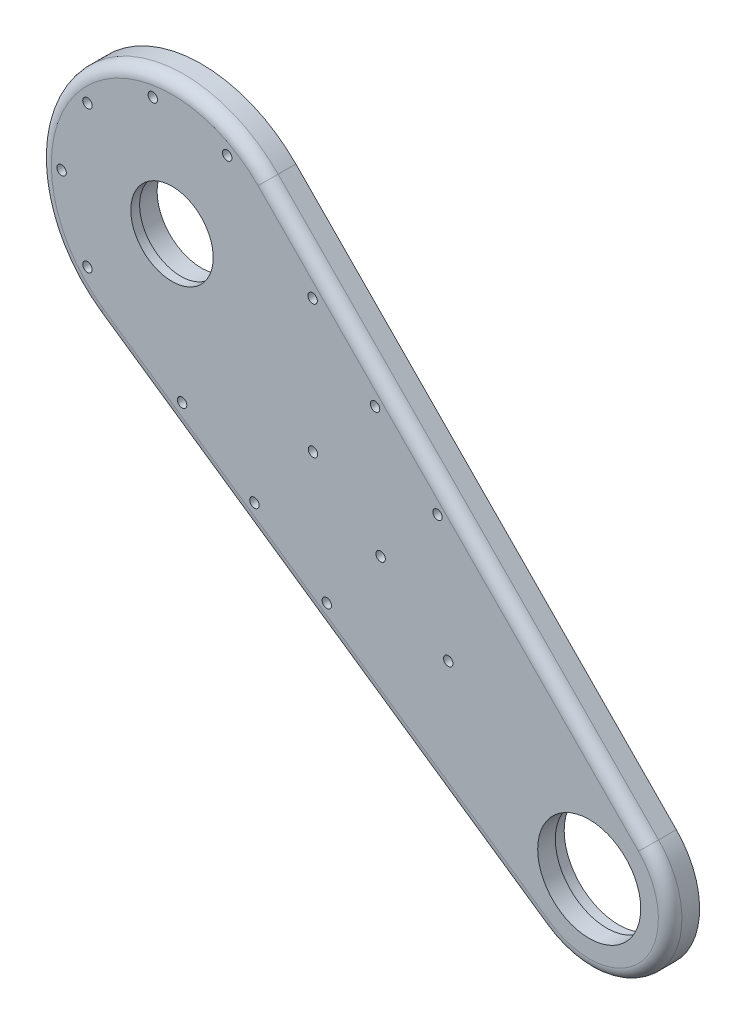
SolidWorks part; units mm, degrees
material "ABS"
ref_plane "Front Plane" through (0, 0, 0) normal (0, 0, 1) x (1, 0, 0)
ref_plane "Top Plane" through (0, 0, 0) normal (0, 1, 0) x (1, 0, 0)
ref_plane "Right Plane" through (0, 0, 0) normal (1, 0, 0) x (0, 0, -1)
ref_plane "Plane1" through (0, 0, 37) normal (0, 0, 1) x (1, 0, 0)
sketch "Sketch1" plane through (0, 0, 37) normal (0, 0, 1) x (1, 0, 0)
  line L1 (26.7138, 26.3177) -> (155.9656, -104.8796) construction
  line L2 (-25.5349, -37.0536) -> (126.1136, -141.5596)
  line L3 (32.0566, 31.5812) -> (161.3084, -99.6161)
  line L4 (-21.2791, -30.878) -> (130.3694, -135.384) construction
  arc A0 (32.0566, 31.5812) -> (-25.5349, -37.0536) centre (0, 0) ccw
  arc A1 (126.1136, -141.5596) -> (161.3084, -99.6161) centre (141.7182, -118.9157) ccw
  circle A5 centre (0, 0) radius 25 construction
  circle A6 centre (0, 0) radius 37.5 construction
  circle A7 centre (141.7182, -118.9157) radius 17.5
  circle A8 centre (70.8591, -59.4579) radius 1.6
  circle A9 centre (93.8404, -78.7415) radius 1.6
  circle A10 centre (47.8778, -40.1742) radius 1.6
  circle A11 centre (141.7182, -118.9157) radius 20 construction
  circle A12 centre (47.768, 4.9466) radius 1.6
  circle A14 centre (3.4233, -47.9013) radius 1.6
  circle A16 centre (68.9739, -16.2739) radius 1.6
  circle A17 centre (90.1797, -37.4944) radius 1.6
  circle A18 centre (28.0039, -65.1001) radius 1.6
  circle A19 centre (52.5844, -82.2989) radius 1.6
  circle A20 centre (116.8218, -98.0251) radius 1.6 construction
  circle A21 centre (0, 0) radius 25 construction
  circle A22 centre (141.7182, -118.9157) radius 17.5 construction
  point P16 (141.7182, -118.9157)
extrude "Boss-Extrude1" add sketch "Sketch1" along normal blind 10
sketch "Sketch2" plane through (0, 0, 37) normal (0, 0, -1) x (-1, 0, 0)
  circle A0 centre (-141.7182, -118.9157) radius 18.5
  dimension "D1" = 37
extrude "Cut-Extrude1" cut sketch "Sketch2" against normal blind 4
sketch "Sketch3" plane through (0, 0, 37) normal (0, 0, -1) x (-1, 0, 0)
  circle A0 centre (-18.75, 32.476) radius 1.6
  circle A1 centre (6.5118, 36.9303) radius 1.6
  circle A2 centre (28.7267, 24.1045) radius 1.6
  circle A3 centre (37.5, 0) radius 1.6
  circle A4 centre (28.7267, -24.1045) radius 1.6
  dimension "D1" = 3.2
  dimension "D2" = 3.2
  dimension "D3" = 3.2
  dimension "D4" = 3.2
  dimension "D5" = 3.2
extrude "Cut-Extrude2" cut sketch "Sketch3" against normal through all
sketch "Sketch4" plane through (0, 0, 37) normal (0, 0, -1) x (-1, 0, 0)
  circle A0 centre (0, 0) radius 14
  circle A1 centre (0, 0) radius 15.0625
  dimension "D1" = 28
  dimension "D2" = 30.125
extrude "Cut-Extrude3" cut sketch "Sketch4" against normal through all contours A0 region at (0, 0, 37)
extrude "Cut-Extrude4" cut sketch "Sketch4<3>" against normal blind 7 contours A1 A0 region at (14.6365, 0, 37)
sketch "Sketch4<3>" plane through (0, 0, 37) normal (0, 0, -1) x (-1, 0, 0) same geometry as "Sketch4"
fillet "Fillet1" radius 4 4 edges at (162.7844, -136.5924, 47) (50.2894, -89.3066, 47) (-34.472, 28.9254, 47) (96.6825, -34.0174, 47)
equation "\"thighLength\"=185"
equation "\"legLength\"=200"
equation "\"m3Thru\"=3.2"
equation "\"m4Thru\"=4.3"
equation "\"shoulder5mm\"=5.1"
equation "\"6706out\"=37.125"
equation "\"6706in\"=30"
equation "\"6904out\"=30.125"
equation "\"6904in\"=17"
equation "\"D1@Sketch3\"=\"m3Thru\""
equation "\"D2@Sketch3\"=\"m3Thru\""
equation "\"D3@Sketch3\"=\"m3Thru\""
equation "\"D4@Sketch3\"=\"m3Thru\""
equation "\"D5@Sketch3\"=\"m3Thru\""
equation "\"D2@Sketch4\"=\"6904out\""
